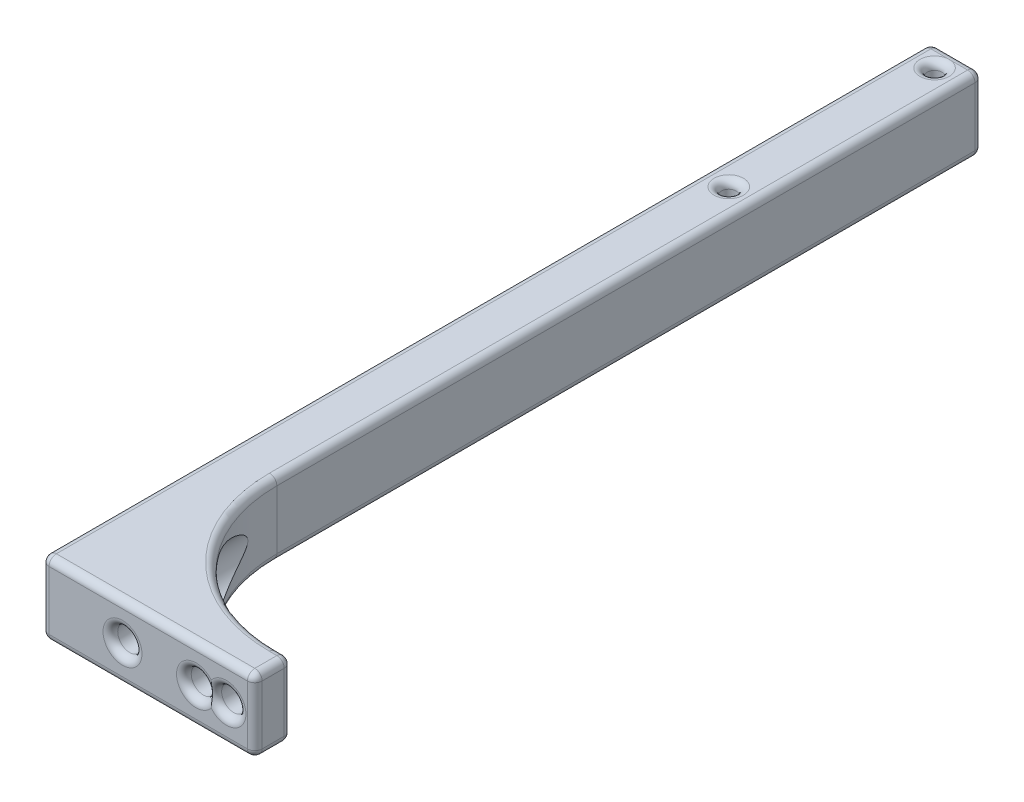
SolidWorks part; units mm, degrees
ref_plane "Front Plane" through (0, 0, 0) normal (0, 0, 1) x (1, 0, 0)
ref_plane "Top Plane" through (0, 0, 0) normal (0, 1, 0) x (1, 0, 0)
ref_plane "Right Plane" through (0, 0, 0) normal (1, 0, 0) x (0, 0, -1)
sketch "Sketch1" plane through (0, 0, 0) normal (0, 1, 0) x (1, 0, 0)
  line L0 (3.5, 0) -> (3.5, 121) construction
  line L1 (0, 0) -> (7, 0)
  line L2 (0, 0) -> (0, 121)
  line L3 (0, 121) -> (7, 121)
  line L4 (7, 0) -> (7, 121)
  circle A0 centre (3.5, 118) radius 1
  circle A1 centre (3.5, 90) radius 1
  dimension "D1" = 2
  dimension "D2" = 28
  dimension "D3" = 7
  dimension "D4" = 3
  dimension "D5" = 90
extrude "Boss-Extrude1" add sketch "Sketch1" along normal blind 10
sketch "Sketch2" plane through (7, 0, 0) normal (1, 0, 0) x (0, 0, -1)
  line L0 (0, 0) -> (121, 0) construction
  line L1 (0, 10) -> (5, 10)
  line L2 (0, 10) -> (0, 0)
  line L3 (0, 0) -> (5, 0)
  line L4 (5, 10) -> (5, 0)
  line L5 (0, 10) -> (0, 0) construction
  line L6 (0, 10) -> (121, 10) construction
  point P7 (0, 0)
  point P8 (0, 0)
  point P11 (5, 10)
  dimension "D1" = 5
extrude "Boss-Extrude2" add sketch "Sketch2" along normal blind 22 and the other way up to surface (7 mm away) other way up to face at (0, 5, -60.5)
sketch "Sketch3" plane through (0, 0, -5) normal (0, 0, -1) x (-1, 0, 0)
  line L0 (-21, 5) -> (-11, 5) construction
  line L2 (-7, 10) -> (-7, 0) construction
  line L3 (-29, 0) -> (-7, 0) construction
  line L6 (-25.14, 5) -> (-21, 5) construction
  circle A0 centre (-21, 5) radius 1.65
  circle A1 centre (-11, 5) radius 1.65
  circle A3 centre (-25.14, 5) radius 1.65
  point P2 (-12.2093, 3)
  point P4 (-18, 3)
  point P10 (0, 0)
  point P11 (0, 0)
  point P12 (0, 0)
  point P14 (0, 0)
  point P15 (-18, 3)
  point P16 (0, 0)
  point P17 (-32.14, 3)
  point P18 (-28, 3)
  point P19 (-18, 3)
  point P20 (0, 0)
  point P21 (-32.14, 3)
  point P22 (0, 0)
  dimension "D1" = 3.3
  dimension "D7" = 14.14
  dimension "D2" = 10
  dimension "D3" = 4
  dimension "D5" = 5
extrude "Cut-Extrude1" cut sketch "Sketch3" against normal blind 20
fillet "Fillet1" radius 20 1 edges at (7, 5, -5)
fillet "Fillet2" radius 1 26 edges at (7, 5, -121) (0, 5, -121) (29, 5, -5) (0, 5, 0) (29, 5, 0) (9.35, 5, 0) (19.35, 5, 0) (3.5, 10, -89) (3.5, 10, -117) (3.5, 10, -121) (7, 10, -73) (12.8579, 10, -10.8579) (28, 10, -5) (29, 10, -2.5) (14.5, 10, 0) (0, 10, -60.5) (3.5, 0, -89) (14.5, 0, 0) (29, 0, -2.5) (28, 0, -5) (12.8579, 0, -10.8579) (7, 0, -73) (3.5, 0, -121) (0, 0, -60.5) (3.5, 0, -117) (23.49, 5, 0)
ref_plane "Plane3" through (0, 0, -5) normal (0, 0, 1) x (1, 0, 0)
sketch "Sketch6" plane through (0, 0, -5) normal (0, 0, 1) x (1, 0, 0)
  circle A0 centre (11, 5) radius 3.5
  arc A1 (23.07, 7.8223) -> (23.07, 2.1777) centre (21, 5) ccw
  arc A2 (23.07, 2.1777) -> (23.07, 7.8223) centre (25.14, 5) ccw
  dimension "D1" = 7
extrude "Cut-Extrude3" cut sketch "Sketch6" against normal through all
